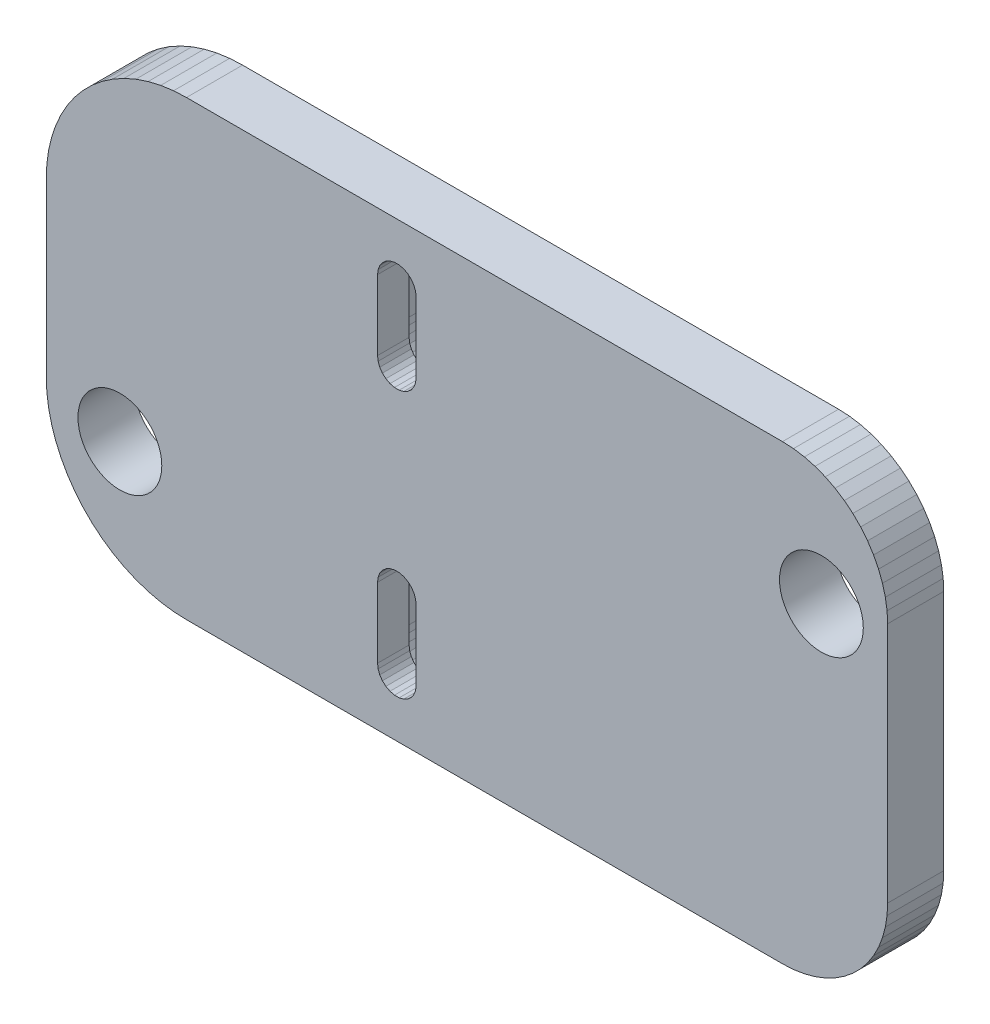
SolidWorks part; units mm, degrees
ref_plane "Front Plane" through (0, 0, 0) normal (0, 0, 1) x (1, 0, 0)
ref_plane "Top Plane" through (0, 0, 0) normal (0, 1, 0) x (1, 0, 0)
ref_plane "Right Plane" through (0, 0, 0) normal (1, 0, 0) x (0, 0, -1)
ref_plane "Plane1" through (0, 0, 8) normal (0, 0, 1) x (1, 0, 0)
sketch "Sketch1" plane through (0, 0, 8) normal (0, 0, 1) x (1, 0, 0)
  line L0 (13.3168, 15.1742) -> (12, 16.0294)
  line L1 (12, 16.0294) -> (10.601, 16.7422)
  line L2 (10.601, 16.7422) -> (9.1353, 17.3048)
  line L3 (9.1353, 17.3048) -> (7.6187, 17.7112)
  line L4 (7.6187, 17.7112) -> (6.0679, 17.9568)
  line L5 (6.0679, 17.9568) -> (4.5, 18.039)
  line L6 (4.5, 18.039) -> (-80.5, 18.039)
  line L7 (-80.5, 18.039) -> (-82.3454, 17.9537)
  line L8 (-82.3454, 17.9537) -> (-84.175, 17.6984)
  line L9 (-84.175, 17.6984) -> (-85.9733, 17.2755)
  line L10 (-85.9733, 17.2755) -> (-87.7248, 16.6884)
  line L11 (-87.7248, 16.6884) -> (-89.4148, 15.9423)
  line L12 (-89.4148, 15.9423) -> (-91.0286, 15.0433)
  line L13 (-91.0286, 15.0433) -> (-92.5527, 13.9993)
  line L14 (-92.5527, 13.9993) -> (-93.9739, 12.8192)
  line L15 (-93.9739, 12.8192) -> (-95.2802, 11.5129)
  line L16 (-95.2802, 11.5129) -> (-96.4603, 10.0917)
  line L17 (-96.4603, 10.0917) -> (-97.5043, 8.5676)
  line L18 (-97.5043, 8.5676) -> (-98.4033, 6.9538)
  line L19 (-98.4033, 6.9538) -> (-99.1494, 5.2638)
  line L20 (-99.1494, 5.2638) -> (-99.7365, 3.5122)
  line L21 (-99.7365, 3.5122) -> (-100.1595, 1.714)
  line L22 (-100.1595, 1.714) -> (-100.4147, -0.1156)
  line L23 (-100.4147, -0.1156) -> (-100.5, -1.961)
  line L24 (-100.5, -1.961) -> (-100.5, -26.461)
  line L25 (-100.5, -26.461) -> (-100.4147, -28.3064)
  line L26 (-100.4147, -28.3064) -> (-100.1595, -30.136)
  line L27 (-100.1595, -30.136) -> (-99.7365, -31.9343)
  line L28 (-99.7365, -31.9343) -> (-99.1494, -33.6858)
  line L29 (-99.1494, -33.6858) -> (-98.4033, -35.3758)
  line L30 (-98.4033, -35.3758) -> (-97.5043, -36.9897)
  line L31 (-97.5043, -36.9897) -> (-96.4603, -38.5137)
  line L32 (-96.4603, -38.5137) -> (-95.2802, -39.9349)
  line L33 (-95.2802, -39.9349) -> (-93.9739, -41.2412)
  line L34 (-93.9739, -41.2412) -> (-92.5527, -42.4214)
  line L35 (-92.5527, -42.4214) -> (-91.0286, -43.4654)
  line L36 (-91.0286, -43.4654) -> (-89.4148, -44.3643)
  line L37 (-89.4148, -44.3643) -> (-87.7248, -45.1105)
  line L38 (-87.7248, -45.1105) -> (-85.9733, -45.6975)
  line L39 (-85.9733, -45.6975) -> (-84.175, -46.1205)
  line L40 (-84.175, -46.1205) -> (-82.3454, -46.3757)
  line L41 (-82.3454, -46.3757) -> (-80.5, -46.461)
  line L42 (-80.5, -46.461) -> (4.5, -46.461)
  line L43 (4.5, -46.461) -> (6.0679, -46.3788)
  line L44 (6.0679, -46.3788) -> (7.6187, -46.1332)
  line L45 (7.6187, -46.1332) -> (9.1353, -45.7269)
  line L46 (9.1353, -45.7269) -> (10.601, -45.1642)
  line L47 (10.601, -45.1642) -> (12, -44.4514)
  line L48 (12, -44.4514) -> (13.3168, -43.5963)
  line L49 (13.3168, -43.5963) -> (14.537, -42.6082)
  line L50 (14.537, -42.6082) -> (15.6472, -41.498)
  line L51 (15.6472, -41.498) -> (16.6353, -40.2778)
  line L52 (16.6353, -40.2778) -> (17.4904, -38.961)
  line L53 (17.4904, -38.961) -> (18.2032, -37.5621)
  line L54 (18.2032, -37.5621) -> (18.7658, -36.0963)
  line L55 (18.7658, -36.0963) -> (19.1722, -34.5797)
  line L56 (19.1722, -34.5797) -> (19.4178, -33.0289)
  line L57 (19.4178, -33.0289) -> (19.5, -31.461)
  line L58 (19.5, -31.461) -> (19.5, 3.039)
  line L59 (19.5, 3.039) -> (19.4178, 4.6069)
  line L60 (19.4178, 4.6069) -> (19.1722, 6.1577)
  line L61 (19.1722, 6.1577) -> (18.7658, 7.6742)
  line L62 (18.7658, 7.6742) -> (18.2032, 9.14)
  line L63 (18.2032, 9.14) -> (17.4904, 10.539)
  line L64 (17.4904, 10.539) -> (16.6353, 11.8558)
  line L65 (16.6353, 11.8558) -> (15.6472, 13.0759)
  line L66 (15.6472, 13.0759) -> (14.537, 14.1862)
  line L67 (14.537, 14.1862) -> (13.3168, 15.1742)
extrude "Boss-Extrude1" add sketch "Sketch1" against normal blind 8
sketch "Sketch2" plane through (0, 0, 0) normal (0, 0, -1) x (-1, 0, 0)
  line L0 (47.1254, -24.1893) -> (46.4783, -24.8364)
  line L1 (46.4783, -24.8364) -> (45.9534, -25.586)
  line L2 (45.9534, -25.586) -> (45.5666, -26.4154)
  line L3 (45.5666, -26.4154) -> (45.3298, -27.2994)
  line L4 (45.3298, -27.2994) -> (45.25, -28.211)
  line L5 (45.25, -28.211) -> (45.25, -38.211)
  line L6 (45.25, -38.211) -> (45.3298, -39.1227)
  line L7 (45.3298, -39.1227) -> (45.5666, -40.0066)
  line L8 (45.5666, -40.0066) -> (45.9534, -40.836)
  line L9 (45.9534, -40.836) -> (46.4783, -41.5856)
  line L10 (46.4783, -41.5856) -> (47.1254, -42.2327)
  line L11 (47.1254, -42.2327) -> (47.875, -42.7576)
  line L12 (47.875, -42.7576) -> (48.7044, -43.1444)
  line L13 (48.7044, -43.1444) -> (49.5883, -43.3813)
  line L14 (49.5883, -43.3813) -> (50.5, -43.461)
  line L15 (50.5, -43.461) -> (51.4117, -43.3813)
  line L16 (51.4117, -43.3813) -> (52.2956, -43.1444)
  line L17 (52.2956, -43.1444) -> (53.125, -42.7576)
  line L18 (53.125, -42.7576) -> (53.8746, -42.2327)
  line L19 (53.8746, -42.2327) -> (54.5217, -41.5856)
  line L20 (54.5217, -41.5856) -> (55.0466, -40.836)
  line L21 (55.0466, -40.836) -> (55.4334, -40.0066)
  line L22 (55.4334, -40.0066) -> (55.6702, -39.1227)
  line L23 (55.6702, -39.1227) -> (55.75, -38.211)
  line L24 (55.75, -38.211) -> (55.75, -28.211)
  line L25 (55.75, -28.211) -> (55.6702, -27.2994)
  line L26 (55.6702, -27.2994) -> (55.4334, -26.4154)
  line L27 (55.4334, -26.4154) -> (55.0466, -25.586)
  line L28 (55.0466, -25.586) -> (54.5217, -24.8364)
  line L29 (54.5217, -24.8364) -> (53.8746, -24.1893)
  line L30 (53.8746, -24.1893) -> (53.125, -23.6644)
  line L31 (53.125, -23.6644) -> (52.2956, -23.2776)
  line L32 (52.2956, -23.2776) -> (51.4117, -23.0408)
  line L33 (51.4117, -23.0408) -> (50.5, -22.961)
  line L34 (50.5, -22.961) -> (49.5883, -23.0408)
  line L35 (49.5883, -23.0408) -> (48.7044, -23.2776)
  line L36 (48.7044, -23.2776) -> (47.875, -23.6644)
  line L37 (47.875, -23.6644) -> (47.1254, -24.1893)
extrude "Cut-Extrude1" cut sketch "Sketch2" against normal blind 3.5
sketch "Sketch3" plane through (0, 0, 8) normal (0, 0, 1) x (1, 0, 0)
  line L0 (-49.5248, -25.6397) -> (-50.1685, -25.4811)
  line L1 (-50.1685, -25.4811) -> (-50.8315, -25.4811)
  line L2 (-50.8315, -25.4811) -> (-51.4752, -25.6397)
  line L3 (-51.4752, -25.6397) -> (-52.0622, -25.9478)
  line L4 (-52.0622, -25.9478) -> (-52.5584, -26.3874)
  line L5 (-52.5584, -26.3874) -> (-52.935, -26.933)
  line L6 (-52.935, -26.933) -> (-53.1701, -27.5529)
  line L7 (-53.1701, -27.5529) -> (-53.25, -28.211)
  line L8 (-53.25, -28.211) -> (-53.25, -38.211)
  line L9 (-53.25, -38.211) -> (-53.1701, -38.8691)
  line L10 (-53.1701, -38.8691) -> (-52.935, -39.489)
  line L11 (-52.935, -39.489) -> (-52.5584, -40.0346)
  line L12 (-52.5584, -40.0346) -> (-52.0622, -40.4742)
  line L13 (-52.0622, -40.4742) -> (-51.4752, -40.7823)
  line L14 (-51.4752, -40.7823) -> (-50.8315, -40.941)
  line L15 (-50.8315, -40.941) -> (-50.1685, -40.941)
  line L16 (-50.1685, -40.941) -> (-49.5248, -40.7823)
  line L17 (-49.5248, -40.7823) -> (-48.9378, -40.4742)
  line L18 (-48.9378, -40.4742) -> (-48.4416, -40.0346)
  line L19 (-48.4416, -40.0346) -> (-48.065, -39.489)
  line L20 (-48.065, -39.489) -> (-47.8299, -38.8691)
  line L21 (-47.8299, -38.8691) -> (-47.75, -38.211)
  line L22 (-47.75, -38.211) -> (-47.75, -28.211)
  line L23 (-47.75, -28.211) -> (-47.8299, -27.5529)
  line L24 (-47.8299, -27.5529) -> (-48.065, -26.933)
  line L25 (-48.065, -26.933) -> (-48.4416, -26.3874)
  line L26 (-48.4416, -26.3874) -> (-48.9378, -25.9478)
  line L27 (-48.9378, -25.9478) -> (-49.5248, -25.6397)
extrude "Cut-Extrude2" cut sketch "Sketch3" against normal through all
sketch "Sketch4" plane through (0, 0, 0) normal (0, 0, -1) x (-1, 0, 0)
  line L0 (47.1254, 13.8107) -> (46.4783, 13.1636)
  line L1 (46.4783, 13.1636) -> (45.9534, 12.414)
  line L2 (45.9534, 12.414) -> (45.5666, 11.5846)
  line L3 (45.5666, 11.5846) -> (45.3298, 10.7006)
  line L4 (45.3298, 10.7006) -> (45.25, 9.789)
  line L5 (45.25, 9.789) -> (45.25, -0.211)
  line L6 (45.25, -0.211) -> (45.3298, -1.1227)
  line L7 (45.3298, -1.1227) -> (45.5666, -2.0066)
  line L8 (45.5666, -2.0066) -> (45.9534, -2.836)
  line L9 (45.9534, -2.836) -> (46.4783, -3.5856)
  line L10 (46.4783, -3.5856) -> (47.1254, -4.2327)
  line L11 (47.1254, -4.2327) -> (47.875, -4.7576)
  line L12 (47.875, -4.7576) -> (48.7044, -5.1444)
  line L13 (48.7044, -5.1444) -> (49.5883, -5.3813)
  line L14 (49.5883, -5.3813) -> (50.5, -5.461)
  line L15 (50.5, -5.461) -> (51.4117, -5.3813)
  line L16 (51.4117, -5.3813) -> (52.2956, -5.1444)
  line L17 (52.2956, -5.1444) -> (53.125, -4.7576)
  line L18 (53.125, -4.7576) -> (53.8746, -4.2327)
  line L19 (53.8746, -4.2327) -> (54.5217, -3.5856)
  line L20 (54.5217, -3.5856) -> (55.0466, -2.836)
  line L21 (55.0466, -2.836) -> (55.4334, -2.0066)
  line L22 (55.4334, -2.0066) -> (55.6702, -1.1227)
  line L23 (55.6702, -1.1227) -> (55.75, -0.211)
  line L24 (55.75, -0.211) -> (55.75, 9.789)
  line L25 (55.75, 9.789) -> (55.6702, 10.7006)
  line L26 (55.6702, 10.7006) -> (55.4334, 11.5846)
  line L27 (55.4334, 11.5846) -> (55.0466, 12.414)
  line L28 (55.0466, 12.414) -> (54.5217, 13.1636)
  line L29 (54.5217, 13.1636) -> (53.8746, 13.8107)
  line L30 (53.8746, 13.8107) -> (53.125, 14.3356)
  line L31 (53.125, 14.3356) -> (52.2956, 14.7224)
  line L32 (52.2956, 14.7224) -> (51.4117, 14.9592)
  line L33 (51.4117, 14.9592) -> (50.5, 15.039)
  line L34 (50.5, 15.039) -> (49.5883, 14.9592)
  line L35 (49.5883, 14.9592) -> (48.7044, 14.7224)
  line L36 (48.7044, 14.7224) -> (47.875, 14.3356)
  line L37 (47.875, 14.3356) -> (47.1254, 13.8107)
extrude "Cut-Extrude3" cut sketch "Sketch4" against normal blind 3.5
sketch "Sketch5" plane through (0, 0, 8) normal (0, 0, 1) x (1, 0, 0)
  line L0 (-50.8315, -2.941) -> (-50.1685, -2.941)
  line L1 (-50.1685, -2.941) -> (-49.5248, -2.7823)
  line L2 (-49.5248, -2.7823) -> (-48.9378, -2.4742)
  line L3 (-48.9378, -2.4742) -> (-48.4416, -2.0346)
  line L4 (-48.4416, -2.0346) -> (-48.065, -1.489)
  line L5 (-48.065, -1.489) -> (-47.8299, -0.8691)
  line L6 (-47.8299, -0.8691) -> (-47.75, -0.211)
  line L7 (-47.75, -0.211) -> (-47.75, 9.789)
  line L8 (-47.75, 9.789) -> (-47.8299, 10.4471)
  line L9 (-47.8299, 10.4471) -> (-48.065, 11.067)
  line L10 (-48.065, 11.067) -> (-48.4416, 11.6126)
  line L11 (-48.4416, 11.6126) -> (-48.9378, 12.0522)
  line L12 (-48.9378, 12.0522) -> (-49.5248, 12.3603)
  line L13 (-49.5248, 12.3603) -> (-50.1685, 12.5189)
  line L14 (-50.1685, 12.5189) -> (-50.8315, 12.5189)
  line L15 (-50.8315, 12.5189) -> (-51.4752, 12.3603)
  line L16 (-51.4752, 12.3603) -> (-52.0622, 12.0522)
  line L17 (-52.0622, 12.0522) -> (-52.5584, 11.6126)
  line L18 (-52.5584, 11.6126) -> (-52.935, 11.067)
  line L19 (-52.935, 11.067) -> (-53.1701, 10.4471)
  line L20 (-53.1701, 10.4471) -> (-53.25, 9.789)
  line L21 (-53.25, 9.789) -> (-53.25, -0.211)
  line L22 (-53.25, -0.211) -> (-53.1701, -0.8691)
  line L23 (-53.1701, -0.8691) -> (-52.935, -1.489)
  line L24 (-52.935, -1.489) -> (-52.5584, -2.0346)
  line L25 (-52.5584, -2.0346) -> (-52.0622, -2.4742)
  line L26 (-52.0622, -2.4742) -> (-51.4752, -2.7823)
  line L27 (-51.4752, -2.7823) -> (-50.8315, -2.941)
extrude "Cut-Extrude4" cut sketch "Sketch5" against normal through all
sketch "Sketch6" plane through (0, 0, 0) normal (0, 0, -1) x (-1, 0, 0)
  line L0 (-7.7629, 6.3563) -> (-8.7359, 6.6543)
  line L1 (-8.7359, 6.6543) -> (-9.7454, 6.7836)
  line L2 (-9.7454, 6.7836) -> (-10.7621, 6.7404)
  line L3 (-10.7621, 6.7404) -> (-11.7569, 6.526)
  line L4 (-11.7569, 6.526) -> (-12.7012, 6.1465)
  line L5 (-12.7012, 6.1465) -> (-13.5678, 5.613)
  line L6 (-13.5678, 5.613) -> (-14.3317, 4.9406)
  line L7 (-14.3317, 4.9406) -> (-14.9711, 4.1488)
  line L8 (-14.9711, 4.1488) -> (-15.4674, 3.2604)
  line L9 (-15.4674, 3.2604) -> (-15.8064, 2.3009)
  line L10 (-15.8064, 2.3009) -> (-15.9784, 1.2978)
  line L11 (-15.9784, 1.2978) -> (-15.9784, 0.2802)
  line L12 (-15.9784, 0.2802) -> (-15.8064, -0.7229)
  line L13 (-15.8064, -0.7229) -> (-15.4674, -1.6824)
  line L14 (-15.4674, -1.6824) -> (-14.9711, -2.5709)
  line L15 (-14.9711, -2.5709) -> (-14.3317, -3.3626)
  line L16 (-14.3317, -3.3626) -> (-13.5678, -4.035)
  line L17 (-13.5678, -4.035) -> (-12.7012, -4.5686)
  line L18 (-12.7012, -4.5686) -> (-11.7569, -4.948)
  line L19 (-11.7569, -4.948) -> (-10.7621, -5.1624)
  line L20 (-10.7621, -5.1624) -> (-9.7454, -5.2056)
  line L21 (-9.7454, -5.2056) -> (-8.7359, -5.0763)
  line L22 (-8.7359, -5.0763) -> (-7.7629, -4.7783)
  line L23 (-7.7629, -4.7783) -> (-6.8542, -4.3202)
  line L24 (-6.8542, -4.3202) -> (-6.036, -3.715)
  line L25 (-6.036, -3.715) -> (-5.3318, -2.9803)
  line L26 (-5.3318, -2.9803) -> (-4.7619, -2.1372)
  line L27 (-4.7619, -2.1372) -> (-4.3427, -1.2099)
  line L28 (-4.3427, -1.2099) -> (-4.0863, -0.225)
  line L29 (-4.0863, -0.225) -> (-4, 0.789)
  line L30 (-4, 0.789) -> (-4.0863, 1.803)
  line L31 (-4.0863, 1.803) -> (-4.3427, 2.7878)
  line L32 (-4.3427, 2.7878) -> (-4.7619, 3.7152)
  line L33 (-4.7619, 3.7152) -> (-5.3318, 4.5583)
  line L34 (-5.3318, 4.5583) -> (-6.036, 5.293)
  line L35 (-6.036, 5.293) -> (-6.8542, 5.8982)
  line L36 (-6.8542, 5.8982) -> (-7.7629, 6.3563)
extrude "Cut-Extrude5" cut sketch "Sketch6" against normal through all
sketch "Sketch7" plane through (0, 0, 0) normal (0, 0, -1) x (-1, 0, 0)
  line L0 (87.2988, -23.8535) -> (86.4322, -24.387)
  line L1 (86.4322, -24.387) -> (85.6683, -25.0594)
  line L2 (85.6683, -25.0594) -> (85.0289, -25.8512)
  line L3 (85.0289, -25.8512) -> (84.5326, -26.7396)
  line L4 (84.5326, -26.7396) -> (84.1936, -27.6991)
  line L5 (84.1936, -27.6991) -> (84.0216, -28.7022)
  line L6 (84.0216, -28.7022) -> (84.0216, -29.7199)
  line L7 (84.0216, -29.7199) -> (84.1936, -30.7229)
  line L8 (84.1936, -30.7229) -> (84.5326, -31.6824)
  line L9 (84.5326, -31.6824) -> (85.0289, -32.5709)
  line L10 (85.0289, -32.5709) -> (85.6683, -33.3626)
  line L11 (85.6683, -33.3626) -> (86.4322, -34.035)
  line L12 (86.4322, -34.035) -> (87.2988, -34.5686)
  line L13 (87.2988, -34.5686) -> (88.2431, -34.948)
  line L14 (88.2431, -34.948) -> (89.2379, -35.1624)
  line L15 (89.2379, -35.1624) -> (90.2546, -35.2056)
  line L16 (90.2546, -35.2056) -> (91.2641, -35.0763)
  line L17 (91.2641, -35.0763) -> (92.2371, -34.7783)
  line L18 (92.2371, -34.7783) -> (93.1458, -34.3202)
  line L19 (93.1458, -34.3202) -> (93.964, -33.7151)
  line L20 (93.964, -33.7151) -> (94.6682, -32.9803)
  line L21 (94.6682, -32.9803) -> (95.2381, -32.1372)
  line L22 (95.2381, -32.1372) -> (95.6573, -31.2099)
  line L23 (95.6573, -31.2099) -> (95.9137, -30.225)
  line L24 (95.9137, -30.225) -> (96, -29.211)
  line L25 (96, -29.211) -> (95.9137, -28.197)
  line L26 (95.9137, -28.197) -> (95.6573, -27.2122)
  line L27 (95.6573, -27.2122) -> (95.2381, -26.2848)
  line L28 (95.2381, -26.2848) -> (94.6682, -25.4417)
  line L29 (94.6682, -25.4417) -> (93.964, -24.707)
  line L30 (93.964, -24.707) -> (93.1458, -24.1018)
  line L31 (93.1458, -24.1018) -> (92.2371, -23.6437)
  line L32 (92.2371, -23.6437) -> (91.2641, -23.3457)
  line L33 (91.2641, -23.3457) -> (90.2546, -23.2164)
  line L34 (90.2546, -23.2164) -> (89.2379, -23.2596)
  line L35 (89.2379, -23.2596) -> (88.2431, -23.474)
  line L36 (88.2431, -23.474) -> (87.2988, -23.8535)
extrude "Cut-Extrude6" cut sketch "Sketch7" against normal through all
sketch "Sketch8" plane through (0, 0, 8) normal (0, 0, 1) x (1, 0, 0)
  line L1 (-96.9049, -21.5658) -> (-80.9198, -21.5658)
  line L2 (-96.9049, -21.5658) -> (-96.9049, -36.7986)
  line L3 (-96.9049, -36.7986) -> (-80.9198, -36.7986)
  line L4 (-80.9198, -21.5658) -> (-80.9198, -36.7986)
  line L5 (1.1428, 8.1165) -> (17.4365, 8.1165)
  line L6 (1.1428, 8.1165) -> (1.1428, -8.3303)
  line L7 (1.1428, -8.3303) -> (17.4365, -8.3303)
  line L8 (17.4365, 8.1165) -> (17.4365, -8.3303)
ref_plane "Plane2" through (0, 0, 12) normal (0, 0, 1) x (1, 0, 0)
sketch "Sketch9" plane through (0, 0, 12) normal (0, 0, 1) x (1, 0, 0)
  circle A0 centre (-90, -29.211) radius 5.9784
  circle A1 centre (10.0527, 0.7799) radius 5.9761
extrude "Boss-Extrude2" add sketch "Sketch8" against normal blind 8
extrude "Cut-Extrude7" cut sketch "Sketch9" against normal blind 12
